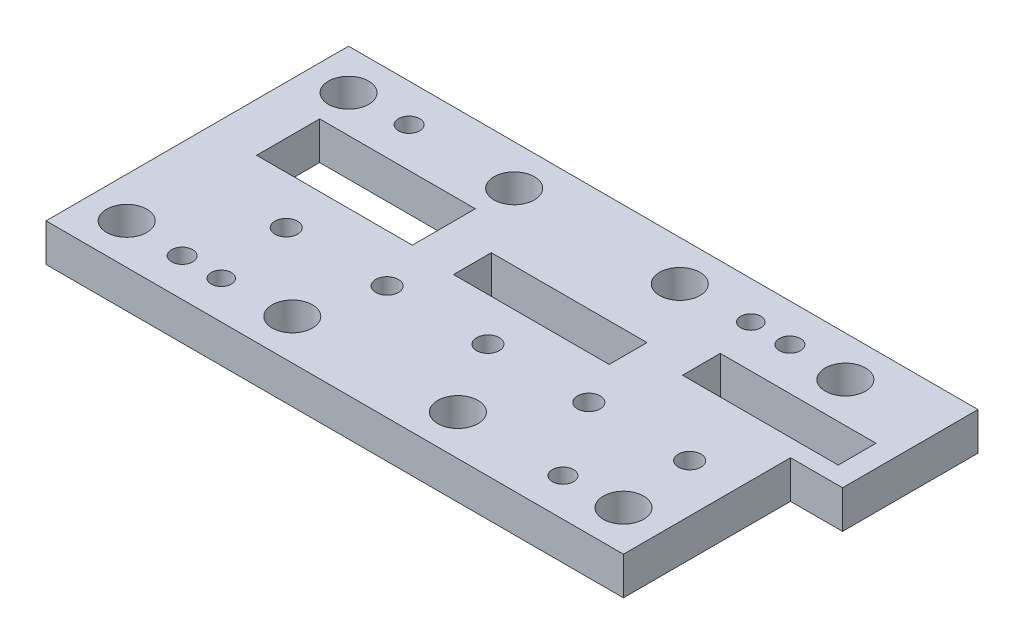
SolidWorks part; units mm, degrees
material "Plain Carbon Steel"
ref_plane "Front Plane" through (0, 0, 0) normal (0, 0, 1) x (1, 0, 0)
ref_plane "Top Plane" through (0, 0, 0) normal (0, 1, 0) x (1, 0, 0)
ref_plane "Right Plane" through (0, 0, 0) normal (1, 0, 0) x (0, 0, -1)
sketch "Sketch1" plane through (0, 0, 0) normal (0, 1, 0) x (1, 0, 0)
  line L0 (-229, 60) -> (-229, -60) construction
  line L1 (-229, -60) -> (0, -60)
  line L2 (-229, -60) -> (-229, 60)
  line L3 (-229, 60) -> (0, 60)
  line L4 (0, -60) -> (0, 60)
  point P4 (0, 0)
  dimension "D1" = 120
extrude "Boss-Extrude1" add sketch "Sketch1" along normal mid plane 15
ref_plane "Plane2" through (-114.5, 0, 0) normal (1, 0, 0) x (0, 0, -1)
sketch "Sketch4" plane through (0, 7.5, 0) normal (0, 1, 0) x (1, 0, 0)
  line L1 (0, 60) -> (20.6325, 60)
  line L2 (0, 60) -> (0, 6.27)
  line L3 (0, 6.27) -> (20.6325, 6.27)
  line L4 (20.6325, 60) -> (20.6325, 6.27)
extrude "Boss-Extrude2" add sketch "Sketch4" against normal up to surface (15 mm away) up to face at (-114.5, -7.5, 0)
sketch "Sketch5" plane through (0, 7.5, 0) normal (0, 1, 0) x (1, 0, 0)
  line L1 (-129.75, 17.3524) -> (-68, 17.3524)
  line L2 (-129.75, 17.3524) -> (-129.75, 2.3524)
  line L3 (-129.75, 2.3524) -> (-68, 2.3524)
  line L4 (-68, 17.3524) -> (-68, 2.3524)
  line L5 (-49.75, 28.191) -> (12, 28.191)
  line L6 (-49.75, 28.191) -> (-49.75, 13.191)
  line L7 (-49.75, 13.191) -> (12, 13.191)
  line L8 (12, 28.191) -> (12, 13.191)
  line L9 (-209.75, 29.28) -> (-148, 29.28)
  line L10 (-209.75, 29.28) -> (-209.75, 4.28)
  line L11 (-209.75, 4.28) -> (-148, 4.28)
  line L12 (-148, 29.28) -> (-148, 4.28)
extrude "Cut-Extrude1" cut sketch "Sketch5" against normal up to next
sketch "Sketch8" plane through (0, 7.5, 0) normal (0, 1, 0) x (1, 0, 0)
  line L3 (-11, 0) -> (11, 0) construction
  line L4 (-114.5, -11) -> (-114.5, 11) construction
  circle A0 centre (-213, 44) radius 8
  dimension "D1" = 16
  dimension "D2" = 44
  dimension "D3" = 98.5
extrude "Cut-Extrude4" cut sketch "Sketch8" against normal up to next
pattern_linear "LPattern2" count 4 spacing 65.677 along (1, 0, 0) count 2 spacing 88 along (0, 0, 1) of "Cut-Extrude4"
hole_wizard "Ø9.0 (9) Diameter Hole1" positions "Sketch11" profile "Sketch10" hole size "Ø9.0" standard "ISO" end condition through all
sketch "Sketch11" plane through (0, 7.5, 0) normal (0, 1, 0) x (1, 0, 0)
  point P0 (-179, -14.72)
  point P3 (-139, -14.72)
  point P6 (-99, -14.72)
  point P9 (-59, -14.72)
  point P12 (-19, -14.72)
sketch "Sketch10" plane through (-179, 7.5, 14.72) normal (1, 0, 0) x (0, 0, 1)
  line L0 (0, 0) -> (0, 15)
  line L1 (0, 15) -> (4.5, 15)
  line L2 (4.5, 15) -> (4.5, 0)
  line L5 (4.5, 0) -> (0, 0)
  line L11 (0, -6.35) -> (0, 107.95) construction
  dimension "Thru Hole Dia." = 9
  dimension "Thru Hole Depth" = 15
hole_wizard "CBORE for M8 Hex Socket Head Cap Screw1" positions "Sketch14" profile "Sketch13" counterbore size "M8" standard "ISO" end condition through all
sketch "Sketch14" plane through (0, -7.5, 0) normal (0, -1, 0) x (-1, 0, 0)
  line L0 (-20.6325, 60) -> (229, 60) construction
  line L1 (229, -60) -> (0, -60) construction
  circle A0 centre (15.969, 44) radius 8 construction
  circle A1 centre (213, 44) radius 8 construction
  point P0 (38.969, 45)
  point P2 (190, 45)
  point P4 (190, -45)
  point P6 (38.969, -45)
  dimension "D1" = 15
  dimension "D2" = 15
  dimension "D3" = 15
  dimension "D4" = 15
sketch "Sketch13" plane through (-38.969, -7.5, -45) normal (1, 0, 0) x (0, 0, -1)
  line L0 (0, 0) -> (0, 15)
  line L1 (0, 15) -> (4.2, 15)
  line L3 (4.2, 15) -> (4.2, 8.6)
  line L4 (4.2, 8.6) -> (7.5, 8.6)
  line L5 (7.5, 8.6) -> (7.5, 0)
  line L7 (7.5, 0) -> (0, 0)
  line L11 (0, -6.35) -> (0, 107.95) construction
  dimension "Thru Hole Dia." = 8.4
  dimension "Thru Hole Depth" = 15
  dimension "C'Bore Dia." = 15
  dimension "C'Bore Depth" = 8.6
hole_wizard "Ø8.0mm Dowel Hole1" positions "Sketch17" profile "Sketch16" hole size "Ø8.0" standard "ISO" end condition through all
sketch "Sketch17" plane through (0, -7.5, 0) normal (0, -1, 0) x (-1, 0, 0)
  line L0 (-20.6325, 60) -> (229, 60) construction
  line L1 (229, -60) -> (0, -60) construction
  circle A0 centre (190, -45) radius 7.5 construction
  circle A1 centre (38.969, 45) radius 7.5 construction
  point P0 (174.5, -45)
  point P2 (54.469, 45)
  point P9 (0, 0)
  dimension "D1" = 8
  dimension "D2" = 8
  dimension "D3" = 15
  dimension "D4" = 15
sketch "Sketch16" plane through (-174.5, -7.5, 45) normal (1, 0, 0) x (0, 0, -1)
  line L0 (0, 0) -> (0, 15)
  line L1 (0, 15) -> (4, 15)
  line L2 (4, 15) -> (4, 0)
  line L5 (4, 0) -> (0, 0)
  line L11 (0, -6.35) -> (0, 107.95) construction
  dimension "Thru Hole Dia." = 8
  dimension "Thru Hole Depth" = 15
